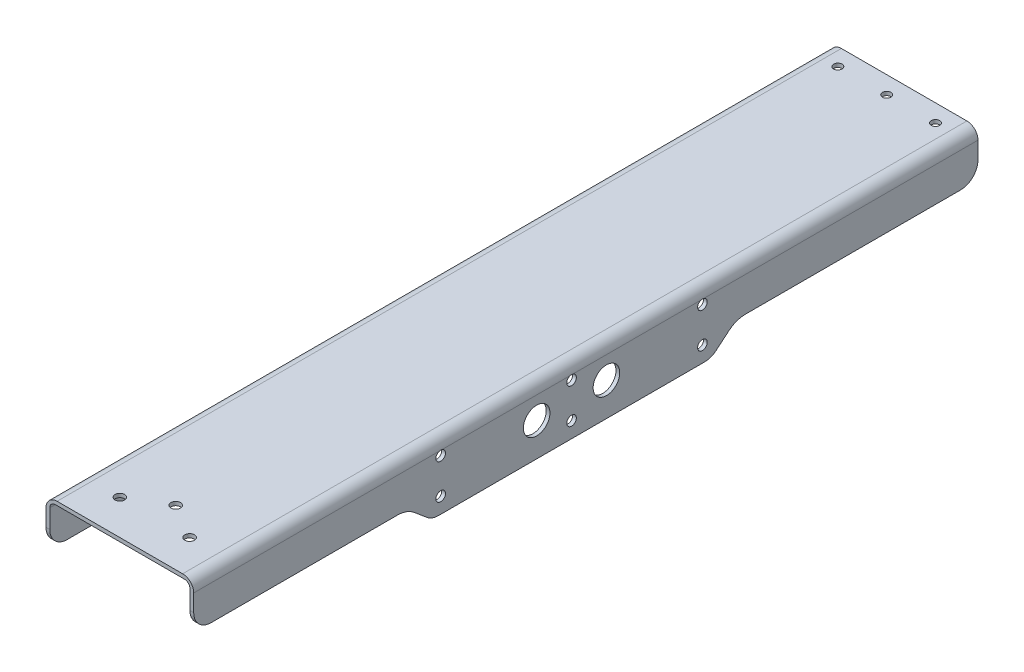
SolidWorks part; units mm, degrees
material "Carbon Fiber, Plain Weave"
ref_plane "Front Plane" through (0, 0, 0) normal (0, 0, 1) x (1, 0, 0)
ref_plane "Top Plane" through (0, 0, 0) normal (0, 1, 0) x (1, 0, 0)
ref_plane "Right Plane" through (0, 0, 0) normal (1, 0, 0) x (0, 0, -1)
ref_axis "Axis1" through (0, 0, -88.99) along (0, 0, 1)
ref_axis "Axis2" through (0, -55, 0) along (0, 1, 0)
ref_axis "Axis3" through (-88.99, 0, 0) along (1, 0, 0)
sketch "Sketch1" plane through (0, 0, 0) normal (0, 0, 1) x (1, 0, 0)
  line L0 (42.3291, -38.1) -> (42.3291, 0)
  line L4 (40.1701, -2.159) -> (40.1701, -38.1)
  line L5 (40.1701, -38.1) -> (42.3291, -38.1)
  line L6 (42.3291, 0) -> (0, 0) construction
  line L7 (0, 0) -> (0, -2.159) construction
  line L8 (-40.1701, -38.1) -> (-42.3291, -38.1)
  line L9 (-40.1701, -2.159) -> (-40.1701, -38.1)
  line L10 (40.1701, -2.159) -> (-40.1701, -2.159)
  line L12 (-42.3291, 0) -> (42.3291, 0)
  line L13 (-42.3291, -38.1) -> (-42.3291, 0)
  dimension "D1" = 2.159
  dimension "D2" = 38.1
  dimension "D3" = 84.6582
extrude "Boss-Extrude1" add sketch "Sketch1" along normal mid plane 449.5
hole_wizard "#11 (0.191) Diameter Hole1" positions "Sketch4" profile "Sketch3" hole size "#11" standard "ANSI Inch" end condition through all
sketch "Sketch4" plane through (0, 0, 0) normal (0, 1, 0) x (1, 0, 0)
  line L0 (-42.3291, 214.75) -> (42.3291, 214.75) construction
  line L4 (0, 214.75) -> (0, 224.75) construction
  line L7 (0, 0) -> (42.3291, 0) construction
  line L8 (42.3291, 224.75) -> (-42.3291, 224.75) construction
  line L10 (-42.3291, -224.75) -> (-42.3291, 224.75) construction
  line L11 (42.3291, -224.75) -> (42.3291, 224.75) construction
  point P0 (28, 214.75)
  point P2 (-28, 214.75)
  point P4 (0, 214.75)
  dimension "D1" = 10
  dimension "D2" = 56
sketch "Sketch3" plane through (28, 0, -214.75) normal (1, 0, 0) x (0, 0, 1)
  line L0 (0, 0) -> (0, 38.1)
  line L1 (0, 38.1) -> (2.4257, 38.1)
  line L2 (2.4257, 38.1) -> (2.4257, 0)
  line L5 (2.4257, 0) -> (0, 0)
  line L11 (0, -6.35) -> (0, 107.95) construction
  dimension "Thru Hole Dia." = 4.8514
  dimension "Thru Hole Depth" = 38.1
hole_wizard "M5 Clearance Hole2" positions "Sketch8" profile "Sketch7" hole size "M5" standard "ANSI Metric" end condition through all
sketch "Sketch8" plane through (0, 0, 0) normal (0, -1, 0) x (-1, 0, 0)
  point P0 (0, -192.75)
  point P3 (-20, -204.75)
  point P6 (20, -204.75)
sketch "Sketch7" plane through (0, 0, 192.75) normal (1, 0, 0) x (0, 0, 1)
  line L0 (0, 0) -> (0, 38.1)
  line L1 (0, 38.1) -> (2.75, 38.1)
  line L2 (2.75, 38.1) -> (2.75, 0)
  line L5 (2.75, 0) -> (0, 0)
  line L11 (0, -6.35) -> (0, 107.95) construction
  dimension "Thru Hole Dia." = 5.5
  dimension "Thru Hole Depth" = 38.1
hole_wizard "M5 Clearance Hole1" positions "Sketch10" profile "Sketch9" hole size "M5" standard "ANSI Metric" end condition through all
sketch "Sketch10" plane through (-42.3291, 0, 0) normal (1, 0, 0) x (0, 0, -1)
  point P0 (66.8, -29.1)
  point P3 (66.8, -9)
  point P5 (-8.2, -29.1)
  point P8 (-8.2, -9)
  point P11 (-83.2, -29.1)
  point P14 (-83.2, -9)
sketch "Sketch9" plane through (-42.3291, -29.1, -66.8) normal (0, 1, 0) x (0, 0, 1)
  line L0 (0, 0) -> (0, 84.6582)
  line L1 (0, 84.6582) -> (2.75, 84.6582)
  line L2 (2.75, 84.6582) -> (2.75, 0)
  line L5 (2.75, 0) -> (0, 0)
  line L11 (0, -6.35) -> (0, 107.95) construction
  dimension "Thru Hole Dia." = 5.5
  dimension "Thru Hole Depth" = 84.6582
sketch "Sketch11" plane through (-42.3291, 0, 0) normal (1, 0, 0) x (0, 0, -1)
  line L0 (-83.2, -9) -> (-8.2, -29.1) construction
  line L1 (-8.2, -29.1) -> (66.8, -9) construction
  line L2 (-8.2, -29.1) -> (-8.2, -9) construction
  line L3 (29.3, -19.05) -> (11.8, -19.05) construction
  circle A0 centre (-28.2, -19.05) radius 7.625
  circle A1 centre (11.8, -19.05) radius 7.625
  dimension "D1" = 15.25
  dimension "D2" = 40
extrude "Cut-Extrude1" cut sketch "Sketch11" along normal through all
fillet "Fillet1" radius 3.175 2 edges at (-40.1701, -2.159, 0) (40.1701, -2.159, 0)
fillet "Fillet2" radius 6.35 2 edges at (-42.3291, 0, 0) (42.3291, 0, 0)
sketch "Sketch12" plane through (0, 0, 0) normal (0, 1, 0) x (1, 0, 0)
  line L0 (-24.1541, -179.75) -> (24.1541, -179.75)
  line L1 (26.3992, -174.3299) -> (-21.909, -126.0217)
  line L2 (-27.3291, -128.2668) -> (-27.3291, -176.575)
  line L4 (27.3291, -176.575) -> (27.3291, -95.994) construction
  line L7 (-26.3992, -100.3184) -> (21.909, -148.6266)
  line L8 (27.3291, -146.3815) -> (27.3291, -98.0733)
  line L9 (24.1541, -94.8983) -> (-24.1541, -94.8983)
  line L10 (0, -179.75) -> (0, -94.8983) construction
  line L11 (0, -137.3242) -> (42.3291, -137.3242) construction
  line L12 (0, -137.3242) -> (0, 164.75) construction
  line L13 (0, 0) -> (42.3291, 0) construction
  line L14 (42.3291, -224.75) -> (42.3291, 224.75) construction
  line L15 (-42.3291, -224.75) -> (-42.3291, -83.9348) construction
  line L16 (35.9791, -224.75) -> (-35.9791, -224.75) construction
  line L17 (42.3291, -83.9348) -> (42.3291, -224.75) construction
  line L18 (42.3291, 66.0652) -> (42.3291, -7.4652) construction
  line L19 (35.9791, 224.75) -> (-35.9791, 224.75) construction
  arc A0 (24.1541, -179.75) -> (26.3992, -174.3299) centre (24.1541, -176.575) ccw
  arc A1 (-21.909, -126.0217) -> (-27.3291, -128.2668) centre (-24.1541, -128.2668) ccw
  arc A2 (-27.3291, -176.575) -> (-24.1541, -179.75) centre (-24.1541, -176.575) ccw
  arc A3 (21.909, -148.6266) -> (27.3291, -146.3815) centre (24.1541, -146.3815) ccw
  arc A4 (27.3291, -98.0733) -> (24.1541, -94.8983) centre (24.1541, -98.0733) ccw
  arc A5 (-24.1541, -94.8983) -> (-26.3992, -100.3184) centre (-24.1541, -98.0733) ccw
  dimension "D1" = 3.175
  dimension "D2" = 15
  dimension "D3" = 15
  dimension "D4" = 45
  dimension "D5" = 15
  dimension "D6" = 60
extrude "Cut-Extrude2" [suppressed] cut sketch "Sketch12" against normal through all
pattern_curve "CrvPattern2" [suppressed] of bodies 117 parameters "D1"=4, "D3"=10, "D2"=1, "D4"=10
ref_plane "Plane1" through (0, 0, -10) normal (0, 0, 1) x (1, 0, 0)
mirror "Mirror1" [suppressed] about plane through (0, 0, -10) normal (0, 0, 1)
sketch "Sketch13" plane through (-42.3291, 0, 0) normal (-1, 0, 0) x (0, 0, 1)
  line L0 (-71.8, -38.1) -> (-81.9188, -29.6093)
  line L1 (224.75, -38.1) -> (-224.75, -38.1) construction
  line L2 (-91.5606, -26.1) -> (-224.75, -26.1)
  line L4 (-224.75, -6.35) -> (-224.75, -38.1) construction
  line L5 (-224.75, -26.1) -> (-224.75, -38.1)
  line L6 (-224.75, -38.1) -> (-71.8, -38.1)
  line L7 (0, 0) -> (0, -38.1) construction
  line L9 (88.2, -38.1) -> (224.75, -38.1)
  line L10 (224.75, -38.1) -> (224.75, -26.1)
  line L11 (224.75, -6.35) -> (224.75, -38.1) construction
  line L12 (224.75, -26.1) -> (107.9606, -26.1)
  line L13 (98.3188, -29.6093) -> (88.2, -38.1)
  line L14 (8.2, -29.1) -> (8.2, -38.1) construction
  arc A1 (-81.9188, -29.6093) -> (-91.5606, -26.1) centre (-91.5606, -41.1) ccw
  arc A2 (107.9606, -26.1) -> (98.3188, -29.6093) centre (107.9606, -41.1) ccw
  dimension "D4" = 15
  dimension "D1" = 160
  dimension "D2" = 140
  dimension "D3" = 12
extrude "Cut-Extrude3" cut sketch "Sketch13" against normal through all
fillet "Fillet3" radius 10 8 edges at (-41.2496, -38.1, -71.8) (41.2496, -38.1, -71.8) (41.2496, -38.1, 88.2) (-41.2496, -38.1, 88.2) (-41.2496, -26.1, -224.75) (41.2496, -26.1, -224.75) (-41.2496, -26.1, 224.75) (41.2496, -26.1, 224.75)
ref_plane "Plane2" [suppressed] through (0, -42.3291, 0) normal (0, 1, 0) x (1, 0, 0)
mirror "Mirror3" [suppressed] about plane through (0, -42.3291, 0) normal (0, 1, 0) of bodies 123
